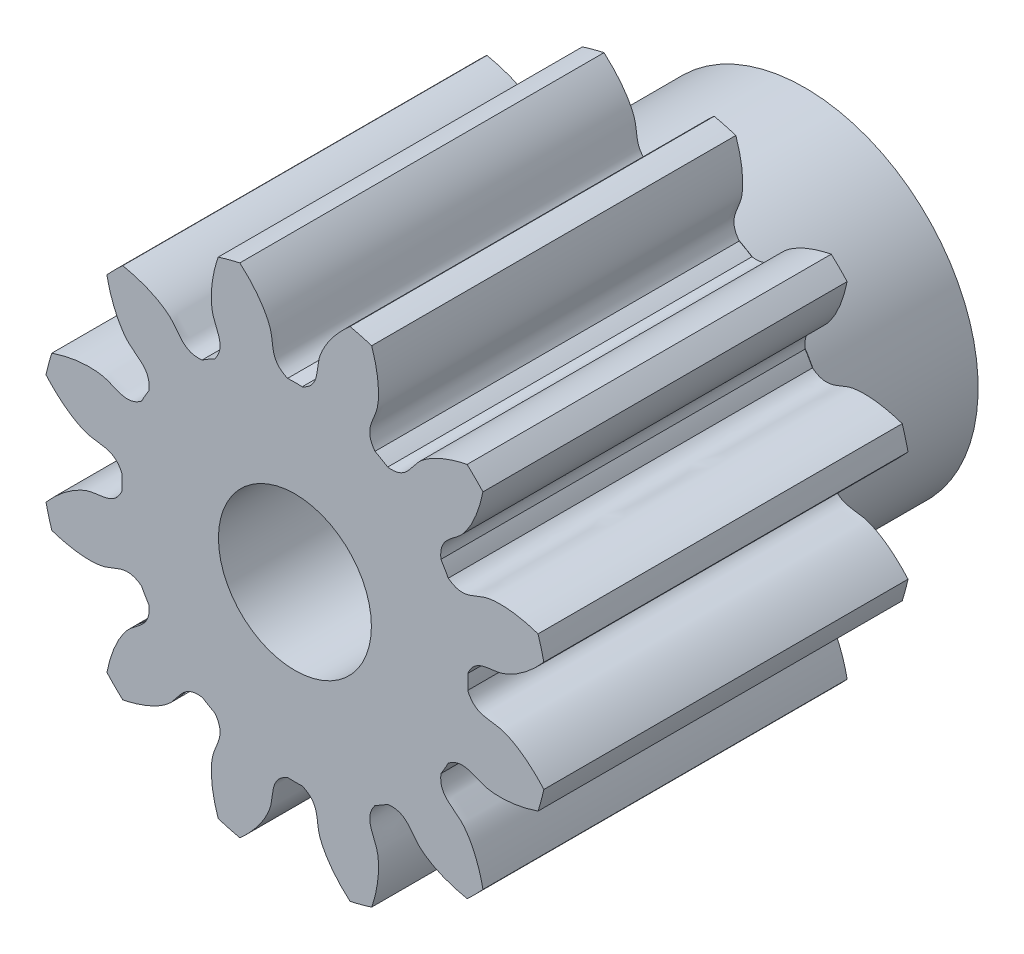
SolidWorks part; units mm, degrees
ref_plane "前视基准面" through (0, 0, 0) normal (0, 0, 1) x (1, 0, 0)
ref_plane "上视基准面" through (0, 0, 0) normal (0, 1, 0) x (1, 0, 0)
ref_plane "右视基准面" through (0, 0, 0) normal (1, 0, 0) x (0, 0, -1)
other "Configuration Table"
sketch "草图1" plane through (0, 0, 0) normal (0, 0, 1) x (1, 0, 0)
  circle A0 centre (0, 0) radius 3.5
extrude "凸台-拉伸1" add sketch "草图1" along normal blind 5
ref_axis "基准轴1" through (0, 0, 5) along (0, 0, -1)
sketch "草图2" plane through (0, 0, 0) normal (0, 0, 1) x (1, 0, 0)
  line L0 (0, 0) -> (0, 3.5) construction
  circle A0 centre (0, 0) radius 3.5 construction
  arc A1 (0.1004, 2.3729) -> (-0.1004, 2.3729) centre (0, 0) ccw
  arc A2 (1.7488, 3.9475) -> (-1.7488, 3.9475) centre (0, 0) ccw
  spline S0 degree 3 poles (0.1004, 2.3729) (0.3404, 2.4747) (0.2872, 2.6724) (0.3381, 2.8447) (0.3413, 2.855) (0.3451, 2.8662) (0.3495, 2.8784) (0.3546, 2.8915) (0.3603, 2.9056) (0.3668, 2.9206) (0.374, 2.9366) (0.3821, 2.9533) (0.3909, 2.971) (0.4007, 2.9894) (0.4114, 3.0086) (0.423, 3.0286) (0.4356, 3.0493) (0.4492, 3.0707) (0.4639, 3.0928) (0.4796, 3.1155) (0.4965, 3.1388) (0.5145, 3.1626) (0.5337, 3.187) (0.554, 3.2119) (0.5756, 3.2372) (0.5985, 3.2629) (0.6226, 3.289) (0.648, 3.3154) (0.6748, 3.342) (0.7028, 3.369) (0.7323, 3.3961) (0.7631, 3.4234) (0.7954, 3.4507) (0.829, 3.4782) (0.8641, 3.5057) (0.9006, 3.5331) (0.9385, 3.5604) (0.978, 3.5877) (1.0189, 3.6147) (1.0613, 3.6416) (1.1052, 3.6681) (1.1506, 3.6944) (1.1975, 3.7203) (1.2459, 3.7457) (1.2958, 3.7707) (1.3472, 3.7952) (1.4001, 3.8191) (1.4546, 3.8424) (1.5105, 3.865) (1.5679, 3.8869) (1.6472, 3.9154) (1.7078, 3.9351) (1.7488, 3.9475) knots 0 0 0 0 0.218015 0.222044 0.226546 0.231522 0.236972 0.242897 0.249295 0.256167 0.263513 0.271332 0.279626 0.288394 0.297636 0.307351 0.317541 0.328204 0.339341 0.350953 0.363038 0.375597 0.38863 0.402137 0.416118 0.430573 0.445502 0.460904 0.476781 0.493132 0.509956 0.527255 0.545027 0.563273 0.581994 0.601188 0.620856 0.640998 0.661614 0.682704 0.704268 0.726305 0.748817 0.771803 0.795262 0.819196 0.843603 0.868484 0.89384 0.919669 0.945972 1 1 1 1
  spline S1 degree 3 poles (-0.1004, 2.3729) (-0.3404, 2.4747) (-0.2872, 2.6724) (-0.3381, 2.8447) (-0.3413, 2.855) (-0.3451, 2.8662) (-0.3495, 2.8784) (-0.3546, 2.8915) (-0.3603, 2.9056) (-0.3668, 2.9206) (-0.374, 2.9366) (-0.3821, 2.9533) (-0.3909, 2.971) (-0.4007, 2.9894) (-0.4114, 3.0086) (-0.423, 3.0286) (-0.4356, 3.0493) (-0.4492, 3.0707) (-0.4639, 3.0928) (-0.4796, 3.1155) (-0.4965, 3.1388) (-0.5145, 3.1626) (-0.5337, 3.187) (-0.554, 3.2119) (-0.5756, 3.2372) (-0.5985, 3.2629) (-0.6226, 3.289) (-0.648, 3.3154) (-0.6748, 3.342) (-0.7028, 3.369) (-0.7323, 3.3961) (-0.7631, 3.4234) (-0.7954, 3.4507) (-0.829, 3.4782) (-0.8641, 3.5057) (-0.9006, 3.5331) (-0.9385, 3.5604) (-0.978, 3.5877) (-1.0189, 3.6147) (-1.0613, 3.6416) (-1.1052, 3.6681) (-1.1506, 3.6944) (-1.1975, 3.7203) (-1.2459, 3.7457) (-1.2958, 3.7707) (-1.3472, 3.7952) (-1.4001, 3.8191) (-1.4546, 3.8424) (-1.5105, 3.865) (-1.5679, 3.8869) (-1.6472, 3.9154) (-1.7078, 3.9351) (-1.7488, 3.9475) knots 0 0 0 0 0.218015 0.222044 0.226546 0.231522 0.236972 0.242897 0.249295 0.256167 0.263513 0.271332 0.279626 0.288394 0.297636 0.307351 0.317541 0.328204 0.339341 0.350953 0.363038 0.375597 0.38863 0.402137 0.416118 0.430573 0.445502 0.460904 0.476781 0.493132 0.509956 0.527255 0.545027 0.563273 0.581994 0.601188 0.620856 0.640998 0.661614 0.682704 0.704268 0.726305 0.748817 0.771803 0.795262 0.819196 0.843603 0.868484 0.89384 0.919669 0.945972 1 1 1 1
extrude "切除-拉伸1" cut sketch "草图2" along normal through all
pattern_circular "阵列(圆周)1" count 12 over 360 about axis through (0, 0, 5) along (0, 0, -1) of "切除-拉伸1"
sketch "草图3" plane through (0, 0, 0) normal (0, 0, 1) x (1, 0, 0)
  circle A0 centre (0, 0) radius 3 construction
  dimension "Dn" = 6
sketch "草图4" plane through (0, 0, 0) normal (0, 0, -1) x (-1, 0, 0)
  circle A0 centre (0, 0) radius 2.38
  dimension "D1" = 4.76
extrude "凸台-拉伸2" add sketch "草图4" along normal blind 2
sketch "草图5" plane through (0, 0, -2) normal (0, 0, -1) x (-1, 0, 0)
  circle A0 centre (0, 0) radius 1.05
  dimension "D1" = 2.1
extrude "切除-拉伸2" cut sketch "草图5" against normal up to next
